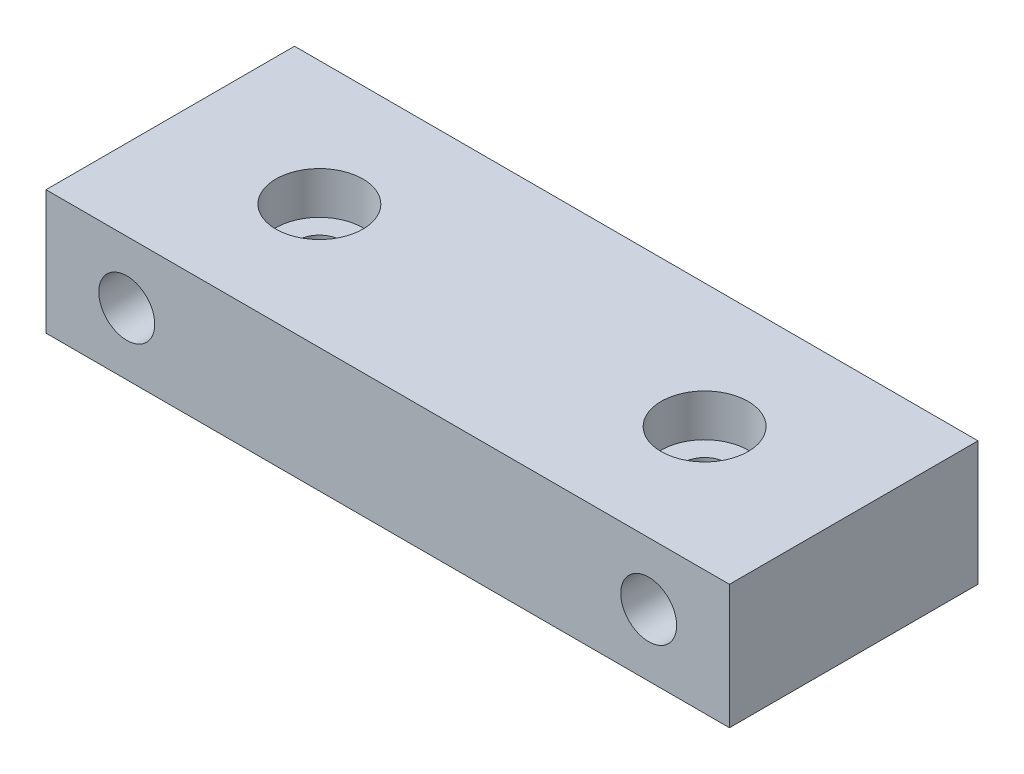
SolidWorks part; units mm, degrees
material "ABS"
ref_plane "Front Plane" through (0, 0, 0) normal (0, 0, 1) x (1, 0, 0)
ref_plane "Top Plane" through (0, 0, 0) normal (0, 1, 0) x (1, 0, 0)
ref_plane "Right Plane" through (0, 0, 0) normal (1, 0, 0) x (0, 0, -1)
sketch "Sketch1" plane through (0, 0, 0) normal (0, 1, 0) x (1, 0, 0)
  line L1 (-27.5, -10) -> (27.5, -10)
  line L2 (-27.5, -10) -> (-27.5, 10)
  line L3 (-27.5, 10) -> (27.5, 10)
  line L4 (27.5, -10) -> (27.5, 10)
  line L5 (-27.5, -10) -> (27.5, 10) construction
  line L6 (-27.5, 10) -> (27.5, -10) construction
  point P0 (0, 0)
  dimension "D1" = 55
  dimension "D2" = 20
extrude "Boss-Extrude1" add sketch "Sketch1" along normal blind 10
sketch "Sketch2" plane through (0, 0, 10) normal (0, 0, 1) x (1, 0, 0)
  line L0 (-27.5, 0) -> (27.5, 0) construction
  line L1 (-27.5, 10) -> (-27.5, 0) construction
  circle A0 centre (-21, 5) radius 2.25
  circle A1 centre (21, 5) radius 2.25
  point P8 (0, 0)
  dimension "D1" = 4.5
  dimension "D4" = 4.5
  dimension "D2" = 5
  dimension "D3" = 6.5
  dimension "D5" = 42
extrude "Cut-Extrude1" cut sketch "Sketch2" against normal through all
sketch "Sketch3" plane through (0, 10, 0) normal (0, 1, 0) x (1, 0, 0)
  line L0 (27.5, -10) -> (27.5, 10) construction
  line L1 (-27.5, 10) -> (-27.5, -10) construction
  circle A0 centre (-15.5, 0) radius 1.75
  circle A1 centre (15.5, 0) radius 1.75
  dimension "D1" = 3.5
  dimension "D2" = 3.5
  dimension "D3" = 12
  dimension "D4" = 12
extrude "Cut-Extrude2" cut sketch "Sketch3" against normal through all
hole_wizard "CBORE for M3 Hex Socket Head Cap Screw1" positions "Sketch4" profile "Sketch5" counterbore size "M3" standard "ISO" end condition through all
sketch "Sketch4" plane through (0, 10, 0) normal (0, 1, 0) x (1, 0, 0)
  point P0 (-15.5, 0)
  point P3 (15.5, 0)
sketch "Sketch5" plane through (-15.5, 10, 0) normal (1, 0, 0) x (0, 0, 1)
  line L0 (0, 0) -> (0, 10)
  line L1 (0, 10) -> (1.7, 10)
  line L3 (1.7, 10) -> (1.7, 3.4)
  line L4 (1.7, 3.4) -> (3.5, 3.4)
  line L5 (3.5, 3.4) -> (3.5, 0)
  line L7 (3.5, 0) -> (0, 0)
  line L11 (0, -6.35) -> (0, 107.95) construction
  dimension "Thru Hole Dia." = 3.4
  dimension "Thru Hole Depth" = 10
  dimension "C'Bore Dia." = 7
  dimension "C'Bore Depth" = 3.4
sketch "Sketch6" plane through (0, 0, -10) normal (0, 0, -1) x (-1, 0, 0)
  line L13 (-16.3812, 5) -> (-18.6906, 9)
  line L14 (-18.6906, 9) -> (-23.3094, 9)
  line L15 (-23.3094, 9) -> (-25.6188, 5)
  line L16 (-25.6188, 5) -> (-23.3094, 1)
  line L17 (-23.3094, 1) -> (-18.6906, 1)
  line L18 (-18.6906, 1) -> (-16.3812, 5)
  line L19 (16.3812, 5) -> (18.6906, 1)
  line L20 (18.6906, 1) -> (23.3094, 1)
  line L21 (23.3094, 1) -> (25.6188, 5)
  line L22 (25.6188, 5) -> (23.3094, 9)
  line L23 (23.3094, 9) -> (18.6906, 9)
  line L24 (18.6906, 9) -> (16.3812, 5)
  circle A0 centre (-21, 5) radius 4 construction
  circle A1 centre (21, 5) radius 4 construction
  dimension "D1" = 8
  dimension "D2" = 8
extrude "Cut-Extrude3" cut sketch "Sketch6" against normal blind 4
